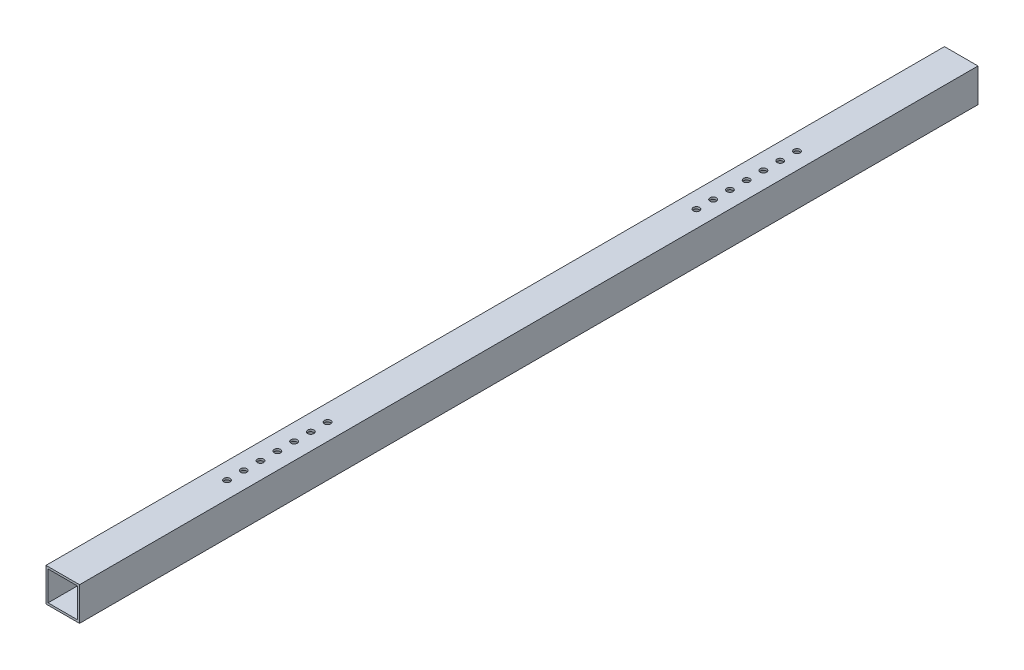
SolidWorks part; units mm, degrees
material "ALUMINUM 6061-T6"
ref_plane "Front Plane" through (0, 0, 0) normal (0, 0, 1) x (1, 0, 0)
ref_plane "Top Plane" through (0, 0, 0) normal (0, 1, 0) x (1, 0, 0)
ref_plane "Right Plane" through (0, 0, 0) normal (1, 0, 0) x (0, 0, -1)
sketch "Sketch1" plane through (0, 0, 0) normal (0, 0, 1) x (1, 0, 0)
  line L1 (-12.7, -12.7) -> (12.7, -12.7)
  line L2 (-12.7, -12.7) -> (-12.7, 12.7)
  line L3 (-12.7, 12.7) -> (12.7, 12.7)
  line L4 (12.7, -12.7) -> (12.7, 12.7)
  line L5 (-12.7, -12.7) -> (12.7, 12.7) construction
  line L6 (-12.7, 12.7) -> (12.7, -12.7) construction
  point P0 (0, 0)
  dimension "D1" = 25.4
  dimension "D2" = 25.4
extrude "Boss-Extrude1" add sketch "Sketch1" along normal mid plane 680.72
sketch "Sketch2" plane through (0, 0, 340.36) normal (0, 0, 1) x (1, 0, 0)
  line L0 (-11.1125, 11.1125) -> (-11.1125, -11.1125)
  line L1 (-12.7, 12.7) -> (12.7, 12.7)
  line L2 (-12.7, 12.7) -> (-12.7, -12.7)
  line L3 (-12.7, -12.7) -> (12.7, -12.7)
  line L4 (12.7, 12.7) -> (12.7, -12.7)
  line L5 (-11.1125, -11.1125) -> (11.1125, -11.1125)
  line L6 (11.1125, 11.1125) -> (11.1125, -11.1125)
  line L7 (-11.1125, 11.1125) -> (11.1125, 11.1125)
  dimension "D1" = 1.5875
extrude "Cut-Extrude1" cut sketch "Sketch2" against normal through all contours L7 L6 L5 L0
sketch "Sketch3" plane through (0, 12.7, 0) normal (0, 1, 0) x (1, 0, 0)
  line L1 (-12.7, -340.36) -> (-12.7, 340.36) construction
  circle A0 centre (0, -215.9) radius 2.3812
  circle A1 centre (0, -203.2) radius 2.3812
  circle A2 centre (0, -190.5) radius 2.3812
  circle A3 centre (0, -177.8) radius 2.3812
  circle A4 centre (0, -165.1) radius 2.3812
  circle A5 centre (0, -152.4) radius 2.3812
  circle A6 centre (0, -139.7) radius 2.3812
  circle A7 centre (0, 139.7) radius 2.3812
  circle A8 centre (0, 152.4) radius 2.3812
  circle A9 centre (0, 165.1) radius 2.3812
  circle A10 centre (0, 177.8) radius 2.3812
  circle A11 centre (0, 190.5) radius 2.3812
  circle A12 centre (0, 215.9) radius 2.3813
  circle A13 centre (0, 203.2) radius 2.3812
  point P32 (-12.7, 0)
  dimension "D1" = 4.7625
  dimension "D2" = 12.7
  dimension "D3" = 12.7
  dimension "D4" = 12.7
  dimension "D5" = 12.7
  dimension "D6" = 12.7
  dimension "D7" = 12.7
  dimension "D8" = 4.7625
  dimension "D9" = 12.7
  dimension "D10" = 12.7
  dimension "D12" = 12.7
  dimension "D13" = 12.7
  dimension "D14" = 12.7
  dimension "D16" = 177.8
  dimension "D11" = 12.7
  dimension "D15" = 355.6
extrude "Cut-Extrude2" cut sketch "Sketch3" against normal through all
